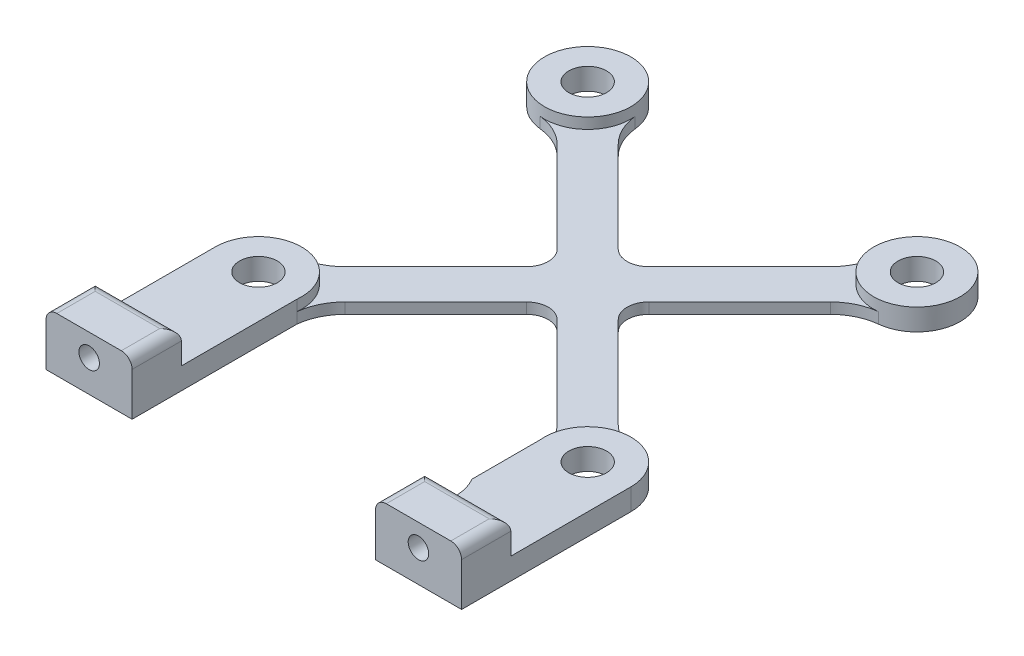
SolidWorks part; units mm, degrees
ref_plane "Front Plane" through (0, 0, 0) normal (0, 0, 1) x (1, 0, 0)
ref_plane "Top Plane" through (0, 0, 0) normal (0, 1, 0) x (1, 0, 0)
ref_plane "Right Plane" through (0, 0, 0) normal (1, 0, 0) x (0, 0, -1)
sketch "Sketch1" plane through (0, 0, 0) normal (0, 1, 0) x (1, 0, 0)
  line L0 (0, 9.8127) -> (0, -12.2658) construction
  line L1 (-32.8724, 0) -> (21.2608, 0) construction
  line L2 (-15.25, 15.25) -> (0, 15.25) construction
  line L3 (-15.25, 15.25) -> (-15.25, 0) construction
  line L4 (-15.25, 15.25) -> (15.25, -15.25) construction
  line L5 (-15.25, -15.25) -> (15.25, 15.25) construction
  line L6 (-16.6642, 13.8358) -> (13.8358, -16.6642)
  line L7 (-13.8358, -16.6642) -> (16.6642, 13.8358)
  line L8 (-13.8358, 16.6642) -> (16.6642, -13.8358)
  line L9 (-16.6642, -13.8358) -> (13.8358, 16.6642)
  circle A0 centre (-15.25, 15.25) radius 1.75
  circle A1 centre (15.25, 15.25) radius 1.75
  circle A2 centre (15.25, -15.25) radius 1.75
  circle A3 centre (-15.25, -15.25) radius 1.75
  circle A4 centre (-15.25, 15.25) radius 4
  circle A5 centre (15.25, 15.25) radius 4
  circle A6 centre (15.25, -15.25) radius 4
  circle A7 centre (-15.25, -15.25) radius 4
  dimension "D1" = 3.5
  dimension "D3" = 8
  dimension "D4" = 2
  dimension "D2" = 30.5
  dimension "D5" = 2
extrude "Boss-Extrude1" add sketch "Sketch1" along normal blind 1 contours A4 A0 | A4 L6 L9 L8 | A7 L7 L6 L9 | L9 L6 L7 L8 | A5 L9 L8 L7 | A6 L8 L7 L6 | A5 A1 | A6 A2 | A7 A3 region at (-6.9798, 0, -6.9798) region at (-18.3337, 0, -17.6162) region at (0, 0, 0) region at (-6.9798, 0, 6.9798) region at (6.9798, 0, 6.9798) region at (-12.5016, 0, 12.5016) region at (6.9798, 0, -6.9798) region at (12.5016, 0, 12.5016) region at (14.7427, 0, -19.1036)
sketch "Sketch2" plane through (0, 1, 0) normal (0, 1, 0) x (1, 0, 0)
  circle A4 centre (-15.25, 15.25) radius 4
  arc A5 (-11.3863, 14.2147) -> (-14.2147, 11.3863) centre (-15.25, 15.25) ccw construction
  circle A6 centre (15.25, 15.25) radius 4
  circle A7 centre (15.25, -15.25) radius 4
  circle A12 centre (-15.25, -15.25) radius 4
  arc A13 (-14.2147, -11.3863) -> (-11.3863, -14.2147) centre (-15.25, -15.25) ccw construction
  arc A14 (11.3863, -14.2147) -> (14.2147, -11.3863) centre (15.25, -15.25) ccw construction
  arc A15 (14.2147, 11.3863) -> (11.3863, 14.2147) centre (15.25, 15.25) ccw construction
  circle A16 centre (-15.25, -15.25) radius 1.75 construction
  circle A17 centre (15.25, -15.25) radius 1.75 construction
  circle A18 centre (15.25, 15.25) radius 1.75 construction
  circle A19 centre (-15.25, 15.25) radius 1.75 construction
  circle A20 centre (-15.25, -15.25) radius 1.75
  circle A21 centre (15.25, -15.25) radius 1.75
  circle A22 centre (15.25, 15.25) radius 1.75
  circle A23 centre (-15.25, 15.25) radius 1.75
  arc M19 (-11.3863, 14.2147) -> (-14.2147, 11.3863) centre (-15.25, 15.25) ccw
  arc M22 (-14.2147, -11.3863) -> (-11.3863, -14.2147) centre (-15.25, -15.25) ccw
  arc M25 (11.3863, -14.2147) -> (14.2147, -11.3863) centre (15.25, -15.25) ccw
  arc M28 (14.2147, 11.3863) -> (11.3863, 14.2147) centre (15.25, 15.25) ccw
  circle M31 centre (-15.25, 15.25) radius 1.75
  circle M32 centre (15.25, 15.25) radius 1.75
  circle M33 centre (15.25, -15.25) radius 1.75
  circle M34 centre (-15.25, -15.25) radius 1.75
extrude "Boss-Extrude2" add sketch "Sketch2" along normal offset from surface (1 mm away) 2 contours A4 M19 M31 | A12 M22 M34 | A7 M25 M33 | A6 M28 M32 region at (-11.3964, 1, -14.7427) region at (17.6162, 1, -12.1663) region at (14.7427, 1, 19.1036) region at (-18.3337, 1, 17.6162) up to face at (0, 0, 0)
fillet "Fillet1" radius 5 8 edges at (11.3863, 0.5, -14.2147) (14.2147, 0.5, 11.3863) (-14.2147, 0.5, 11.3863) (11.3863, 0.5, 14.2147) (14.2147, 0.5, -11.3863) (-11.3863, 0.5, 14.2147) (-11.3863, 0.5, -14.2147) (-14.2147, 0.5, -11.3863)
fillet "Fillet2" radius 2 4 edges at (0, 0.5, -2.8284) (2.8284, 0.5, 0) (0, 0.5, 2.8284) (-2.8284, 0.5, 0)
sketch "Sketch3" plane through (0, 0, 0) normal (0, -1, 0) x (1, 0, 0)
  line L0 (0, 20.9881) -> (0, -14.4185) construction
  line L1 (-25.1, 30.93) -> (25.1, 30.93) construction
  line L2 (-25.1, 30.93) -> (25.1, 30.93)
  line L3 (-11.2723, 15.6721) -> (-11.2723, 30.93)
  line L4 (-19.25, 15.25) -> (-19.25, 30.93)
  line L5 (11.2723, 15.6721) -> (11.2723, 30.93)
  line L6 (19.25, 15.25) -> (19.25, 30.93)
  line L8 (-9.8358, -12.6642) -> (-1.4142, -4.2426)
  line L9 (1.4142, -4.2426) -> (9.8358, -12.6642)
  line L10 (12.6642, -9.8358) -> (4.2426, -1.4142)
  line L11 (4.2426, 1.4142) -> (12.6642, 9.8358)
  line L12 (9.8358, 12.6642) -> (1.4142, 4.2426)
  line L13 (-1.4142, 4.2426) -> (-9.8358, 12.6642)
  line L14 (-12.6642, 9.8358) -> (-4.2426, 1.4142)
  line L15 (-4.2426, -1.4142) -> (-12.6642, -9.8358)
  line L16 (-9.8358, -12.6642) -> (-1.4142, -4.2426)
  line L17 (1.4142, -4.2426) -> (9.8358, -12.6642)
  line L18 (12.6642, -9.8358) -> (4.2426, -1.4142)
  line L19 (4.2426, 1.4142) -> (12.6642, 9.8358)
  line L20 (9.8358, 12.6642) -> (1.4142, 4.2426)
  line L21 (-1.4142, 4.2426) -> (-9.8358, 12.6642)
  line L22 (-12.6642, 9.8358) -> (-4.2426, 1.4142)
  line L23 (-4.2426, -1.4142) -> (-12.6642, -9.8358)
  arc A16 (-15.6721, -11.2723) -> (-11.2723, -15.6721) centre (-15.25, -15.25) ccw
  arc A17 (-9.8358, -12.6642) -> (-11.2723, -15.6721) centre (-6.3003, -16.1997) ccw
  arc A18 (1.4142, -4.2426) -> (-1.4142, -4.2426) centre (0, -5.6569) ccw
  arc A19 (11.2723, -15.6721) -> (9.8358, -12.6642) centre (6.3003, -16.1997) ccw
  arc A20 (11.2723, -15.6721) -> (15.6721, -11.2723) centre (15.25, -15.25) ccw
  arc A21 (12.6642, -9.8358) -> (15.6721, -11.2723) centre (16.1997, -6.3003) ccw
  arc A22 (4.2426, 1.4142) -> (4.2426, -1.4142) centre (5.6569, 0) ccw
  arc A23 (15.6721, 11.2723) -> (12.6642, 9.8358) centre (16.1997, 6.3003) ccw
  arc A24 (15.6721, 11.2723) -> (11.2723, 15.6721) centre (15.25, 15.25) ccw
  arc A25 (9.8358, 12.6642) -> (11.2723, 15.6721) centre (6.3003, 16.1997) ccw
  arc A26 (-1.4142, 4.2426) -> (1.4142, 4.2426) centre (0, 5.6569) ccw
  arc A27 (-11.2723, 15.6721) -> (-9.8358, 12.6642) centre (-6.3003, 16.1997) ccw
  arc A28 (-11.2723, 15.6721) -> (-15.6721, 11.2723) centre (-15.25, 15.25) ccw
  arc A29 (-12.6642, 9.8358) -> (-15.6721, 11.2723) centre (-16.1997, 6.3003) ccw
  arc A30 (-4.2426, -1.4142) -> (-4.2426, 1.4142) centre (-5.6569, 0) ccw
  arc A31 (-15.6721, -11.2723) -> (-12.6642, -9.8358) centre (-16.1997, -6.3003) ccw
  arc A32 (-15.6721, -11.2723) -> (-11.2723, -15.6721) centre (-15.25, -15.25) ccw
  arc A33 (-9.8358, -12.6642) -> (-11.2723, -15.6721) centre (-6.3003, -16.1997) ccw
  arc A34 (1.4142, -4.2426) -> (-1.4142, -4.2426) centre (0, -5.6569) ccw
  arc A35 (11.2723, -15.6721) -> (9.8358, -12.6642) centre (6.3003, -16.1997) ccw
  arc A36 (11.2723, -15.6721) -> (15.6721, -11.2723) centre (15.25, -15.25) ccw
  arc A37 (12.6642, -9.8358) -> (15.6721, -11.2723) centre (16.1997, -6.3003) ccw
  arc A38 (4.2426, 1.4142) -> (4.2426, -1.4142) centre (5.6569, 0) ccw
  arc A39 (15.6721, 11.2723) -> (12.6642, 9.8358) centre (16.1997, 6.3003) ccw
  arc A40 (15.6721, 11.2723) -> (11.2723, 15.6721) centre (15.25, 15.25) ccw
  arc A41 (9.8358, 12.6642) -> (11.2723, 15.6721) centre (6.3003, 16.1997) ccw
  arc A42 (-1.4142, 4.2426) -> (1.4142, 4.2426) centre (0, 5.6569) ccw
  arc A43 (-11.2723, 15.6721) -> (-9.8358, 12.6642) centre (-6.3003, 16.1997) ccw
  arc A44 (-11.2723, 15.6721) -> (-15.6721, 11.2723) centre (-15.25, 15.25) ccw
  arc A45 (-12.6642, 9.8358) -> (-15.6721, 11.2723) centre (-16.1997, 6.3003) ccw
  arc A46 (-4.2426, -1.4142) -> (-4.2426, 1.4142) centre (-5.6569, 0) ccw
  arc A47 (-15.6721, -11.2723) -> (-12.6642, -9.8358) centre (-16.1997, -6.3003) ccw
  arc M37 (15.6721, 11.2723) -> (11.2723, 15.6721) centre (15.25, 15.25) ccw
  arc M43 (-11.2723, 15.6721) -> (-15.6721, 11.2723) centre (-15.25, 15.25) ccw
  dimension "D1" = 0
extrude "Boss-Extrude3" add sketch "Sketch3" against normal up to surface (2 mm away) contours M37 | L4 L3 L2 M43 region at (-15.2637, 0, 24.6338) region at (15.2637, 0, 24.6338) up to face at (15.25, 2, 19.25)
sketch "Sketch4" plane through (0, 2, 0) normal (0, 1, 0) x (1, 0, 0)
  circle A0 centre (7.48, -24.18) radius 4.38
  circle A1 centre (7.48, -24.18) radius 3.88 construction
  dimension "D1" = 0.5
extrude "Cut-Extrude1" cut sketch "Sketch4" against normal up to next
sketch "Sketch5" plane through (0, 2, 0) normal (0, 1, 0) x (1, 0, 0)
  line L0 (-11.2723, -15.6721) -> (-11.2723, -30.93) construction
  line L1 (-19.25, -30.93) -> (-11.2723, -30.93)
  line L2 (-19.25, -30.93) -> (-19.25, -26.3715)
  line L3 (-19.25, -26.3715) -> (-11.2723, -26.3715)
  line L4 (-11.2723, -30.93) -> (-11.2723, -26.3715)
  line L6 (19.25, -30.93) -> (11.2723, -30.93)
  line L7 (19.25, -30.93) -> (19.25, -26.3715)
  line L8 (19.25, -26.3715) -> (11.2723, -26.3715)
  line L9 (11.2723, -30.93) -> (11.2723, -26.3715)
extrude "Boss-Extrude4" add sketch "Sketch5" along normal blind 3
sketch "Sketch6" plane through (0, 0, 30.93) normal (0, 0, 1) x (1, 0, 0)
  line L0 (-19.25, 2.95) -> (19.25, 2.95) construction
  line L3 (0, 0) -> (0, 2.95) construction
  line L4 (-11.2723, 2) -> (-19.25, 2) construction
  line L5 (-19.25, 5) -> (-19.25, 0) construction
  circle A0 centre (-15.25, 2.95) radius 0.95
  circle A1 centre (15.25, 2.95) radius 0.95
  point P2 (0, 0)
  point P5 (0, 0)
  point P13 (0, 0)
  dimension "D1" = 30.5
  dimension "D2" = 1.9
fillet "Fillet3" radius 1 6 edges at (19.25, 5, 28.6507) (11.2723, 5, 28.6507) (-11.2723, 5, 28.6507) (-19.25, 5, 28.6507) (15.2612, 5, 26.3715) (-15.2612, 5, 26.3715)
sketch "Sketch7" [suppressed] plane through (0, 0, 0) normal (0, -1, 0) x (1, 0, 0)
  line L0 (-15.25, 32.93) -> (-15.25, 17) construction
  line L1 (-14.2, 32.93) -> (-16.3, 32.93) construction
  line L2 (0, 0) -> (0, 38.1559) construction
  line L3 (-19.25, 30.93) -> (-11.2723, 30.93) construction
  line L4 (-15.5, 32.93) -> (-15, 32.93)
  line L5 (-15.5, 32.93) -> (-15.5, 30.93)
  line L6 (-15.5, 30.93) -> (-15, 30.93)
  line L7 (-15, 32.93) -> (-15, 30.93)
  line L8 (-15.25, 32.93) -> (-15.25, 30.93) construction
  line L9 (15.5, 32.93) -> (15, 32.93)
  line L10 (15, 32.93) -> (15, 30.93)
  line L11 (15.5, 30.93) -> (15, 30.93)
  line L12 (15.5, 32.93) -> (15.5, 30.93)
  circle A0 centre (-15.25, 15.25) radius 1.75 construction
  dimension "D1" = 0.5
extrude "Boss-Extrude6" [suppressed] add sketch "Sketch7" against normal up to body
extrude "Cut-Extrude2" cut sketch "Sketch6" against normal up to vertex (4.5585 mm away) contours A0 | A1 region at (-15.25, 2.95, 30.93) region at (15.25, 2.95, 30.93) up to point (-11.2723, 2, 26.3715)
